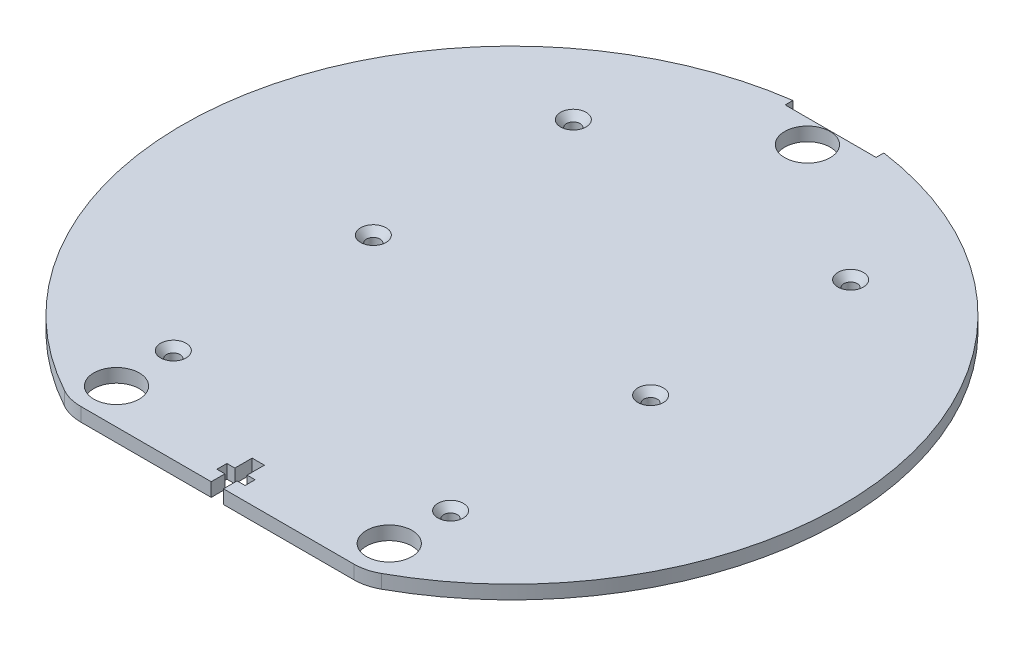
SolidWorks part; units mm, degrees
material "ABS"
ref_plane "Front Plane" through (0, 0, 0) normal (0, 0, 1) x (1, 0, 0)
ref_plane "Top Plane" through (0, 0, 0) normal (0, 1, 0) x (1, 0, 0)
ref_plane "Right Plane" through (0, 0, 0) normal (1, 0, 0) x (0, 0, -1)
sketch "Sketch1" plane through (0, 0, 0) normal (0, 1, 0) x (1, 0, 0)
  line L0 (0, -85) -> (0, 0) construction
  line L1 (30.03, -64.8129) -> (-30.03, -64.8129)
  arc A0 (34.8348, -63.5829) -> (-34.8348, -63.5829) centre (0, 0) ccw
  circle A1 centre (0, -85) radius 38.25 construction
  arc A2 (30.03, -64.8129) -> (34.8348, -63.5829) centre (30.03, -54.8129) ccw
  arc A3 (-30.03, -64.8129) -> (-34.8348, -63.5829) centre (-30.03, -54.8129) cw
  point P12 (-32.4891, -64.8129)
  dimension "D1" = 145
  dimension "D3" = 76.5
  dimension "D4" = 10
  dimension "D2" = 85
extrude "Boss-Extrude1" add sketch "Sketch1" along normal blind 3
sketch "Sketch2" plane through (0, 3, 0) normal (0, 1, 0) x (1, 0, 0)
  line L1 (-30.5, -44) -> (30.5, -44) construction
  line L2 (-30.5, -44) -> (-30.5, 44) construction
  line L3 (-30.5, 44) -> (30.5, 44) construction
  line L4 (30.5, -44) -> (30.5, 44) construction
  line L5 (-30.5, -44) -> (30.5, 44) construction
  line L6 (-30.5, 44) -> (30.5, -44) construction
  circle A0 centre (-30.5, 44) radius 1.5
  circle A1 centre (30.5, 44) radius 1.5
  circle A2 centre (30.5, 0) radius 1.5
  circle A3 centre (30.5, -44) radius 1.5
  circle A4 centre (-30.5, -44) radius 1.5
  circle A5 centre (-30.5, 0) radius 1.5
  point P0 (0, 0)
  dimension "D3" = 3
  dimension "D1" = 61
  dimension "D2" = 88
extrude "Cut-Extrude1" cut sketch "Sketch2" against normal through all
chamfer "Chamfer1" distance 1.5 angle 41 6 edges at (30.5, 3, -42.5) (30.5, 3, 1.5) (30.5, 3, 45.5) (-30.5, 3, 45.5) (-30.5, 3, 1.5) (-30.5, 3, -42.5) first distance on face at (30.5, 0, -42.5) first distance on face at (30.5, 0, 1.5) first distance on face at (30.5, 0, 45.5) first distance on face at (-30.5, 0, 45.5) first distance on face at (-30.5, 0, 1.5) first distance on face at (-30.5, 0, -42.5)
sketch "Sketch3" plane through (0, 3, 0) normal (0, 1, 0) x (1, 0, 0)
  line L0 (-30.03, -64.8129) -> (30.03, -64.8129) construction
  line L1 (1.35, -61.8129) -> (3.1, -61.8129)
  line L2 (-3.1, -59.6129) -> (-1.35, -59.6129)
  line L3 (-3.1, -59.6129) -> (-3.1, -61.8129)
  line L4 (-3.1, -61.8129) -> (-1.35, -61.8129)
  line L5 (3.1, -59.6129) -> (3.1, -61.8129)
  line L6 (-1.35, -64.8129) -> (1.35, -64.8129)
  line L7 (-1.35, -64.8129) -> (-1.35, -61.8129)
  line L8 (1.35, -59.6129) -> (3.1, -59.6129)
  line L9 (1.35, -64.8129) -> (1.35, -61.8129)
  line L11 (-1.35, -59.6129) -> (-1.35, -55.8129)
  line L12 (-1.35, -55.8129) -> (1.35, -55.8129)
  line L13 (1.35, -59.6129) -> (1.35, -55.8129)
  point P10 (0, -64.8129)
  point P14 (0, -64.8129)
  dimension "D1" = 2.7
  dimension "D2" = 6.2
  dimension "D3" = 2.2
  dimension "D4" = 3
  dimension "D5" = 9
extrude "Cut-Extrude2" cut sketch "Sketch3" against normal through all
sketch "Sketch4" plane through (0, 3, 0) normal (0, 1, 0) x (1, 0, 0)
  line L1 (-10, 71.807) -> (10, 71.807)
  line L2 (-10, 71.807) -> (-10, 70.107)
  line L3 (-10, 70.107) -> (10, 70.107)
  line L4 (10, 71.807) -> (10, 70.107)
  arc A0 (34.8348, -63.5829) -> (-34.8348, -63.5829) centre (0, 0) ccw construction
  dimension "D1" = 1.7
  dimension "D2" = 20
extrude "Cut-Extrude3" cut sketch "Sketch4" against normal through all
sketch "Sketch5" plane through (0, 3, 0) normal (0, 1, 0) x (1, 0, 0)
  line L0 (0, 0) -> (0, 65) construction
  circle A0 centre (0, 65) radius 5
  circle A1 centre (30, -57) radius 5
  circle A2 centre (-30, -57) radius 5
  dimension "D1" = 10
  dimension "D2" = 65
  dimension "D3" = 57
  dimension "D4" = 30
extrude "Cut-Extrude4" cut sketch "Sketch5" against normal through all
equation "\"smallPulleyTeeth\"= 30"
equation "\"largePulleyTeeth\"= 30"
equation "\"eighthThick\"= 3.0mm"
equation "\"sixteenthThick\" = 1.7mm"
equation "\"quarterThick\"=6.0mm"
equation "\"OD\" = 145mm"
equation "\"puckAngle\" = 60.5deg"
equation "\"puckDiam\" = 76.5mm"
equation "\"puckDist\" = 85mm"
equation "\"scoopFillet\" = 5mm"
equation "\"axlePress\" = 5.9mm"
equation "\"press\" = 0.2mm"
equation "\"wheelClear\" = 0.3mm"
equation "\"10-32clear\" = 4.8mm"
equation "\"10-32tap\" = 4.45mm"
equation "\"6-32clear\" = 3.3mm"
equation "\"8-32clear\" = 4.0mm"
equation "\"4-40clear\" = 3.0mm"
equation "\"wheelHeight\" = 22mm"
equation "\"wheelWell\" = 65mm"
equation "\"ledSmall\" = 3.1mm"
equation "\"ledLarge\" = 4.2mm"
equation "\"ledLength\" = 4.2mm"
equation "\"D1@Sketch1\"=\"OD\""
equation "\"D1@Boss-Extrude1\"=\"eighthThick\""
equation "\"D3@Sketch2\"=\"4-40clear\""
equation "\"D3@Sketch1\"=\"puckDiam\""
equation "\"D2@Sketch1\"=\"puckDist\""
equation "\"4-40close\" = 2.7mm"
equation "\"4-40nutThick\" = 2.2mm"
equation "\"4-40nutWidth\" = 6.2mm"
equation "\"D1@Sketch4\"=\"sixteenthThick\""
equation "\"D1@Sketch3\"=\"4-40close\""
equation "\"4-40insertHeight\" = 3.5mm"
equation "\"4-40insert\" = 4mm"
equation "\"D2@Sketch3\"=\"4-40nutWidth\""
equation "\"D3@Sketch3\"=\"4-40nutThick\""
